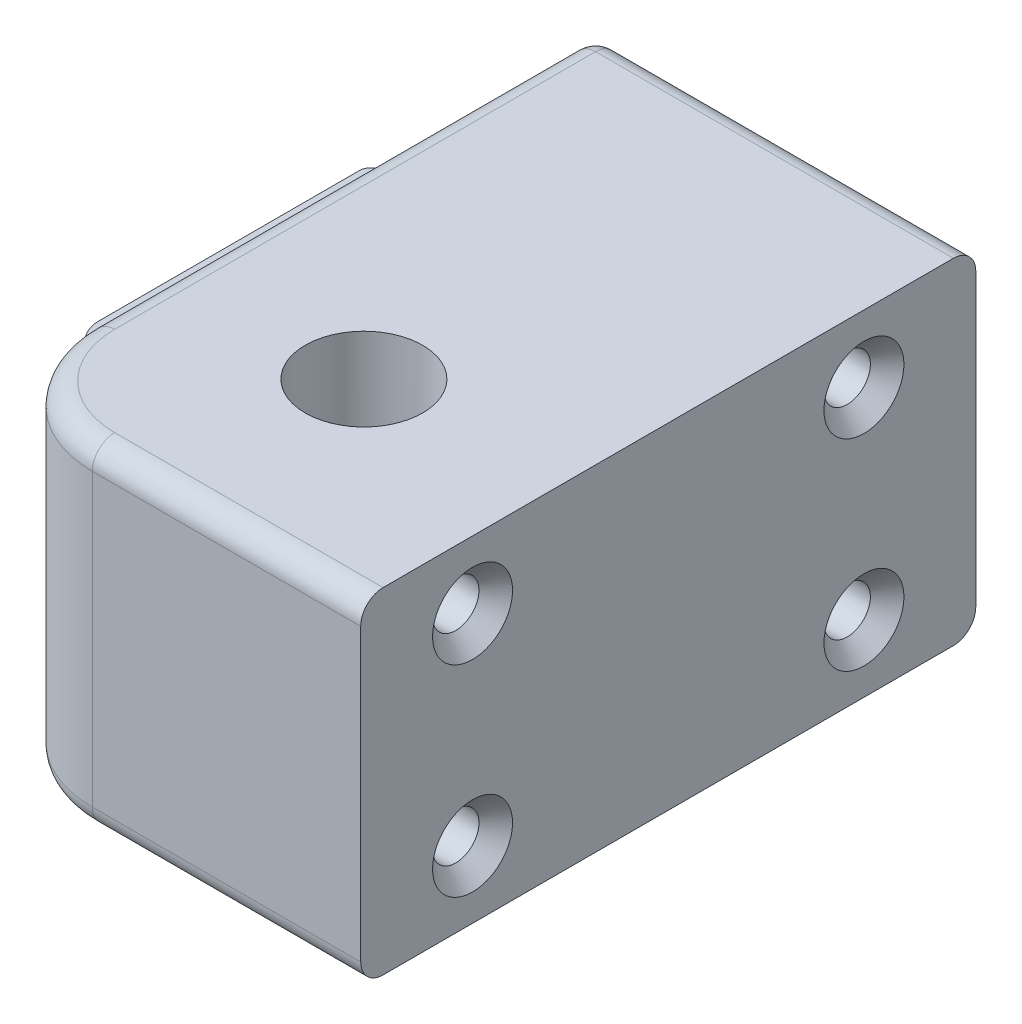
SolidWorks part; units mm, degrees
ref_plane "Front Plane" through (0, 0, 0) normal (0, 0, 1) x (1, 0, 0)
ref_plane "Top Plane" through (0, 0, 0) normal (0, 1, 0) x (1, 0, 0)
ref_plane "Right Plane" through (0, 0, 0) normal (1, 0, 0) x (0, 0, -1)
sketch "Sketch1" plane through (0, 0, 0) normal (0, 0, 1) x (1, 0, 0)
  line L1 (17, -15) -> (-17, -15)
  line L2 (17, -15) -> (17, 15)
  line L3 (17, 15) -> (-17, 15)
  line L4 (-17, -15) -> (-17, 15)
  dimension "D1" = 34
  dimension "D2" = 30
  dimension "D3" = 15
  dimension "D4" = 17
extrude "Boss-Extrude1" add sketch "Sketch1" along normal blind 55
sketch "Sketch2" plane through (0, 0, 0) normal (0, 0, -1) x (-1, 0, 0)
  line L0 (-17, -15) -> (-17, 15) construction
  line L1 (17, -15) -> (-17, -15) construction
  circle A4 centre (-12, 9) radius 2 construction
  circle A5 centre (-12, -9) radius 2 construction
  circle A6 centre (12, -9) radius 2 construction
  circle A7 centre (12, 9) radius 2 construction
  circle A8 centre (12, -9) radius 2.1
  circle A9 centre (12, 9) radius 2.1
  circle A10 centre (-12, -9) radius 2.1
  circle A11 centre (-12, 9) radius 2.1
  dimension "D1" = 4
  dimension "D2" = 5
  dimension "D3" = 29
  dimension "D4" = 6
  dimension "D5" = 24
  dimension "D6" = 0.1
extrude "Cut-Extrude1" cut sketch "Sketch2" against normal blind 6
sketch "Sketch5" plane through (0, -15, 0) normal (0, -1, 0) x (1, 0, 0)
  line L0 (17, 55) -> (17, 0) construction
  line L1 (-17, 0) -> (17, 0) construction
  circle A1 centre (0, 37.7136) radius 11 construction
  circle A3 centre (0, 37.7136) radius 11.15
  dimension "D1" = 22
  dimension "D2" = 17
  dimension "D3" = 37.7136
  dimension "D4" = 0.15
extrude "Cut-Extrude2" cut sketch "Sketch5" against normal blind 12.5
sketch "Sketch6" plane through (0, 15, 0) normal (0, 1, 0) x (1, 0, 0)
  line L0 (-17, -55) -> (-17, 0) construction
  line L1 (17, 0) -> (-17, 0) construction
  circle A1 centre (0, -37.7136) radius 5.1 construction
  circle A2 centre (0, -37.7136) radius 5.25
  dimension "D1" = 10.2
  dimension "D2" = 17
  dimension "D3" = 37.7136
  dimension "D4" = 0.15
extrude "Cut-Extrude3" cut sketch "Sketch6" against normal blind 17.5
sketch "Sketch7" plane through (0, -2.5, 0) normal (0, -1, 0) x (1, 0, 0)
  circle A4 centre (7.9785, 38.3002) radius 1.75 construction
  circle A5 centre (-0.5866, 45.6921) radius 1.75 construction
  circle A6 centre (-7.9785, 37.127) radius 1.75 construction
  circle A7 centre (0.5866, 29.7351) radius 1.75 construction
  circle A8 centre (-7.9785, 37.127) radius 2.1
  circle A9 centre (-0.5866, 45.6921) radius 2.1
  circle A10 centre (7.9785, 38.3002) radius 2.1
  circle A11 centre (0.5866, 29.7351) radius 2.1
  circle A12 centre (0, 37.7136) radius 5.25 construction
  dimension "D2" = 4.2
  dimension "D3" = 0.5866
  dimension "D4" = 7.9785
  dimension "D5" = 0.5866
  dimension "D6" = 7.9785
  dimension "D7" = 0.5866
  dimension "D8" = 7.9785
  dimension "D9" = 0.5866
  dimension "D10" = 7.9785
  dimension "D1" = 0.35
extrude "Cut-Extrude4" cut sketch "Sketch7" against normal blind 6
chamfer "Chamfer1" distance 1 angle 45 4 edges at (7.9785, -2.5, 36.2002) (-0.5866, -2.5, 43.5921) (-7.9785, -2.5, 35.027) (0.5866, -2.5, 27.6351)
chamfer "Chamfer2" distance 1 angle 45 4 edges at (9.9, -9, 0) (-14.1, -9, 0) (-14.1, 9, 0) (9.9, 9, 0)
fillet "Fillet1" radius 10 1 edges at (-17, 0, 55)
fillet "Fillet2" radius 2 9 edges at (-17, 15, 22.5) (5, 15, 55) (5, -15, 55) (-17, -15, 22.5) (0, -15, 0) (-17, 0, 0) (0, 15, 0) (-14.0711, 15, 52.0711) (-14.0711, -15, 52.0711)
sketch "Sketch8" plane through (17, 0, 0) normal (1, 0, 0) x (0, 0, -1)
  line L1 (-45, 9) -> (-10, 9) construction
  line L2 (-45, 9) -> (-45, -9) construction
  line L3 (-45, -9) -> (-10, -9) construction
  line L4 (-10, 9) -> (-10, -9) construction
  line L5 (-45, 9) -> (-10, -9) construction
  line L6 (-45, -9) -> (-10, 9) construction
  line L7 (-53, 15) -> (-2, 15) construction
  circle A0 centre (-45, 9) radius 2.075
  circle A1 centre (-10, 9) radius 2.075
  circle A2 centre (-10, -9) radius 2.075
  circle A3 centre (-45, -9) radius 2.075
  point P0 (-27.5, 0)
  point P9 (0, 0)
  point P10 (-33.591, 0)
  point P14 (-27.5, 15)
  dimension "D1" = 4.15
  dimension "D2" = 35
  dimension "D3" = 18
extrude "Cut-Extrude5" cut sketch "Sketch8" against normal blind 6.5
chamfer "Chamfer3" distance 1.5 angle 45 4 edges at (17, 9, 42.925) (17, -9, 42.925) (17, -9, 7.925) (17, 9, 7.925)
sketch "Sketch9" plane through (0, 0, 0) normal (0, 1, 0) x (1, 0, 0)
  line L0 (-17, -40.0491) -> (-24.3539, -40.0491)
  line L1 (-17, -2) -> (-17, -45) construction
  line L2 (-24.3539, -40.0491) -> (-24.3539, -12.7622)
  line L3 (-24.3539, -12.7622) -> (-17, -12.7622)
  line L4 (-17, -12.7622) -> (-17, -40.0491)
  line L5 (-20.6, -35) -> (-20.6, -19)
  circle A1 centre (-20.6, -35) radius 1.625
  circle A2 centre (-20.6, -19) radius 1.625
  dimension "D3" = 3.25
  dimension "D1" = 3.6
  dimension "D2" = 16
extrude "Boss-Extrude2" add sketch "Sketch9" along normal blind 3 from offset 4 contours L4 L3 L2 L0 A2 A1 region at (-20.6839, 0, 26.3521)
mirror "Mirror1" about plane through (0, 0, 0) normal (0, 1, 0) of "Boss-Extrude2"
fillet "Fillet3" radius 3 4 edges at (-24.3539, 5.5, 40.0491) (-17, 5.5, 40.0491) (-17, -5.5, 40.0491) (-24.3539, -5.5, 40.0491)
fillet "Fillet4" radius 1 4 edges at (-24.3539, 5.5, 12.7622) (-17, 5.5, 12.7622) (-17, -5.5, 12.7622) (-24.3539, -5.5, 12.7622)
sketch "Sketch10" plane through (0, 7, 0) normal (0, 1, 0) x (1, 0, 0)
  line L1 (-17.725, -20.6599) -> (-17.725, -17.3401)
  line L2 (-17.725, -17.3401) -> (-20.6, -15.6802)
  line L3 (-20.6, -15.6802) -> (-23.475, -17.3401)
  line L4 (-23.475, -17.3401) -> (-23.475, -20.6599)
  line L5 (-23.475, -20.6599) -> (-20.6, -22.3198)
  line L6 (-20.6, -22.3198) -> (-17.725, -20.6599)
  line L7 (-17.725, -36.6599) -> (-17.725, -33.3401)
  line L8 (-17.725, -33.3401) -> (-20.6, -31.6802)
  line L9 (-20.6, -31.6802) -> (-23.475, -33.3401)
  line L10 (-23.475, -33.3401) -> (-23.475, -36.6599)
  line L11 (-23.475, -36.6599) -> (-20.6, -38.3198)
  line L12 (-20.6, -38.3198) -> (-17.725, -36.6599)
  circle A0 centre (-20.6, -19) radius 2.875 construction
  circle A1 centre (-20.6, -35) radius 2.875 construction
  dimension "D1" = 5.75
extrude "Cut-Extrude6" cut sketch "Sketch10" against normal blind 2
